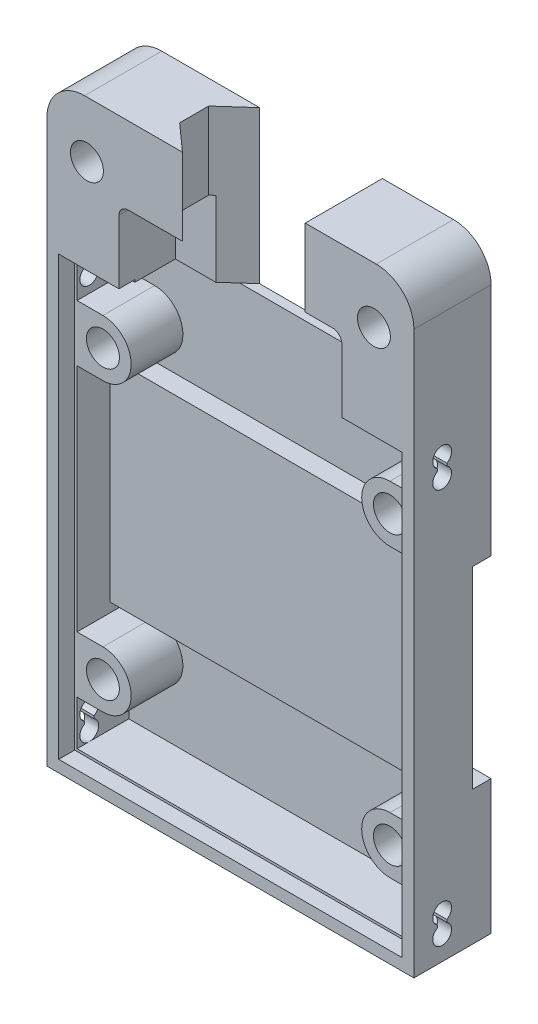
SolidWorks part; units mm, degrees
ref_plane "Front Plane" through (0, 0, 0) normal (0, 0, 1) x (1, 0, 0)
ref_plane "Top Plane" through (0, 0, 0) normal (0, 1, 0) x (1, 0, 0)
ref_plane "Right Plane" through (0, 0, 0) normal (1, 0, 0) x (0, 0, -1)
sketch "Sketch1" plane through (0, 0, 0) normal (0, 0, 1) x (1, 0, 0)
  line L0 (15.25, -20.35) -> (18, -20.35)
  line L1 (-19.5, -32.6) -> (19.5, -32.6)
  line L2 (-19.5, -32.6) -> (-19.5, 31.1)
  line L3 (-19.5, 31.1) -> (19.5, 31.1)
  line L4 (19.5, -32.6) -> (19.5, 31.1)
  line L5 (-15.25, -20.35) -> (-18, -20.35)
  line L6 (15.25, -26.35) -> (18, -26.35)
  line L7 (15.5, 31.1) -> (-15.5, 31.1) construction
  line L8 (-18, -31.1) -> (-18, 29.6)
  line L9 (-18, 29.6) -> (18, 29.6)
  line L10 (18, -31.1) -> (18, 29.6)
  line L11 (-18, -31.1) -> (18, -31.1)
  line L12 (-18, 14.9) -> (18, 14.9)
  line L13 (7.85, 14.9) -> (-4.95, 14.9) construction
  line L14 (-15.25, 4.15) -> (-18, 4.15)
  line L15 (-15.25, 10.15) -> (-18, 10.15)
  line L16 (15.25, 10.15) -> (18, 10.15)
  line L17 (15.25, 4.15) -> (18, 4.15)
  line L18 (-15.25, -26.35) -> (-18, -26.35)
  arc A0 (19.5, 27.1) -> (15.5, 31.1) centre (15.5, 27.1) ccw construction
  arc A1 (-15.5, 31.1) -> (-19.5, 27.1) centre (-15.5, 27.1) ccw construction
  arc A2 (19.5, 27.1) -> (15.5, 31.1) centre (15.5, 27.1) ccw
  arc A3 (-15.5, 31.1) -> (-19.5, 27.1) centre (-15.5, 27.1) ccw
  arc A4 (-15.5, 29.6) -> (-18, 27.1) centre (-15.5, 27.1) ccw
  arc A5 (18, 27.1) -> (15.5, 29.6) centre (15.5, 27.1) ccw
  circle A6 centre (-15.25, -23.35) radius 1.75
  circle A7 centre (15.25, -23.35) radius 1.75
  circle A8 centre (-15.25, 7.15) radius 1.75
  circle A9 centre (15.25, 7.15) radius 1.75
  circle A10 centre (15.25, 25.15) radius 1.75
  circle A11 centre (-15.25, 25.15) radius 1.75
  circle A12 centre (-15.25, -23.35) radius 3
  circle A13 centre (15.25, -23.35) radius 3
  circle A14 centre (15.25, 7.15) radius 3
  circle A15 centre (-15.25, 7.15) radius 3
  dimension "D2" = 1.5
  dimension "D4" = 6
  dimension "D3" = 3.5
  dimension "D1" = 1.5
extrude "Base shape" add sketch "Sketch1" along normal up to surface (8.2 mm away) contours L10 A5 L9 A4 L8 L12 A11 A10 | L3 A3 L2 L1 L4 A2 A15 L8 L9 L10 A14 A13 L11 A12 | A4 L9 L8 | A5 L10 L9 | A15 L15 L8 | A15 L8 A8 | A15 L8 L14 | L8 A15 | A14 L17 L10 | L10 A14 A9 | L10 A14 | A14 L10 L16 | A13 L6 L10 | L10 A13 A7 | L10 A13 | A13 L10 L0 | A12 L8 L18 | A12 L8 A6 | L8 A12 | A12 L5 L8 region at (16.8481, -20.9099, 0) region at (17.3601, -20.8437, 0) region at (17.3601, -25.8563, 0) region at (18.1004, -23.35, 0) region at (17.3601, 4.6437, 0) region at (16.8481, 4.7099, 0) region at (18.1004, 7.15, 0) region at (17.3601, 9.6563, 0) region at (-17.3601, -25.8563, 0) region at (0, 22.1041, 0) region at (-18.1004, -23.35, 0) region at (-17.9169, -23.35, 0) region at (17.4416, 29.0416, 0) region at (-17.3601, -20.8437, 0) region at (-17.3601, 9.6563, 0) region at (-17.4416, 29.0416, 0) region at (-16.8481, 9.5901, 0) region at (-18.1004, 7.15, 0) region at (-17.3601, 4.6437, 0) region at (-18.7531, -2.75, 0)
sketch "Sketch3" plane through (19.5, 0, 0) normal (1, 0, 0) x (0, 0, -1)
  line L1 (0, -18.35) -> (-2, -18.35)
  line L2 (0, -18.35) -> (0, 2.15)
  line L3 (0, 2.15) -> (-2, 2.15)
  line L4 (-2, -18.35) -> (-2, 2.15)
  line L5 (0, -18.35) -> (2, -18.35) construction
  line L6 (0, 2.15) -> (2, 2.15) construction
  line L7 (0, -32.6) -> (0, 27.1) construction
  dimension "D1" = 2
extrude "Strap cut" cut sketch "Sketch3" against normal through all
sketch "Sketch4" plane through (0, 31.1, 0) normal (0, 1, 0) x (1, 0, 0)
  line L2 (7.95, 0) -> (-5.0998, 0)
  line L4 (-15.5, 0) -> (15.5, 0) construction
  line L5 (-15.5, -8.2) -> (15.5, -8.2) construction
  line L6 (7.95, -8.2) -> (-5.0998, -8.2)
  line L12 (7.95, -8.3) -> (7.95, 0.1)
  line L13 (7.95, 0.1) -> (-4.9883, 0.1)
  line L14 (-4.9883, 0.1) -> (-7.95, -2.5553)
  line L15 (-7.95, -2.5553) -> (-7.95, -5.6447)
  line L16 (-7.95, -5.6447) -> (-4.9883, -8.3)
  line L17 (-4.9883, -8.3) -> (7.95, -8.3)
  line L18 (7.95, -8.3) -> (7.95, 0.1)
  line L19 (7.95, 0.1) -> (-4.9883, 0.1)
  line L20 (-4.9883, 0.1) -> (-7.95, -2.5553)
  line L21 (-7.95, -2.5553) -> (-7.95, -5.6447)
  line L22 (-7.95, -5.6447) -> (-4.9883, -8.3)
  line L23 (-4.9883, -8.3) -> (7.95, -8.3)
  dimension "D1" = 0.1
extrude "XT60 cut" cut sketch "Sketch4" against normal up to next contours L21 L22 L18 L20 region at (0.4142, 31.1, 4.1)
sketch "Sketch5" plane through (19.5, 0, 0) normal (1, 0, 0) x (0, 0, -1)
  line L1 (-8.2, -32.6) -> (-8.2, 27.1) construction
  line L2 (-6.2, -31.1) -> (-4.2, -31.1)
  line L3 (-6.2, -31.1) -> (-6.2, -27.1)
  line L4 (-6.2, -27.1) -> (-4.2, -27.1)
  line L5 (-4.2, -31.1) -> (-4.2, -27.1)
  line L6 (-8.2, -31.1) -> (0, -31.1) construction
  line L7 (-8.2, 14.9) -> (0, 14.9) construction
  line L8 (-6.2, 14.9) -> (-4.2, 14.9)
  line L9 (-6.2, 14.9) -> (-6.2, 10.9)
  line L10 (-6.2, 10.9) -> (-4.2, 10.9)
  line L11 (-4.2, 14.9) -> (-4.2, 10.9)
  line L14 (-5.2, -27.1) -> (-5.2, -31.1) construction
  line L15 (-5.2, 14.9) -> (-5.2, 10.9) construction
  line L16 (-5.7, -31.1) -> (-4.7, -31.1)
  line L17 (-5.7, -31.1) -> (-5.7, -27.1)
  line L18 (-5.7, -27.1) -> (-4.7, -27.1)
  line L19 (-4.7, -31.1) -> (-4.7, -27.1)
  line L20 (-5.7, -31.1) -> (-4.7, -27.1) construction
  line L21 (-5.7, -27.1) -> (-4.7, -31.1) construction
  line L23 (-5.7, 10.9) -> (-4.7, 10.9)
  line L24 (-5.7, 10.9) -> (-5.7, 14.9)
  line L25 (-5.7, 14.9) -> (-4.7, 14.9)
  line L26 (-4.7, 10.9) -> (-4.7, 14.9)
  line L27 (-5.7, 10.9) -> (-4.7, 14.9) construction
  line L28 (-5.7, 14.9) -> (-4.7, 10.9) construction
  circle A0 centre (-5.2, -28.1) radius 1
  circle A1 centre (-5.2, -30.1) radius 1
  circle A2 centre (-5.2, 13.9) radius 1
  circle A3 centre (-5.2, 11.9) radius 1
  point P20 (-5.2, -29.1)
  point P31 (-5.2, 12.9)
  dimension "D3" = 4
  dimension "D1" = 2
  dimension "D2" = 2
  dimension "D4" = 1
extrude "Power wires cut" cut sketch "Sketch5" against normal through all contours A2 L26 | L26 A2 L24 | L24 A2 | A3 A2 L24 | A3 L26 A2 | L26 A3 L24 | L24 A3 | A3 L26 | A0 L19 | L19 A0 L17 | L17 A0 | L19 A1 L17 | L17 A1 | A1 L19 | A1 L19 A0 | A1 A0 L17 region at (19.5, -30.1, 5.905) region at (19.5, -30.1, 5.2) region at (19.5, -28.1, 5.905) region at (19.5, -29.1, 5.5767) region at (19.5, -30.1, 4.495) region at (19.5, -28.1, 5.2) region at (19.5, -29.1, 4.8233) region at (19.5, -28.1, 4.495) region at (19.5, 13.9, 5.905) region at (19.5, 13.9, 5.2) region at (19.5, 11.9, 5.905) region at (19.5, 12.9, 5.5767) region at (19.5, 13.9, 4.495) region at (19.5, 11.9, 5.2) region at (19.5, 12.9, 4.8233) region at (19.5, 11.9, 4.495)
sketch "Sketch6" plane through (0, 0, 8.2) normal (0, 0, 1) x (1, 0, 0)
  line L0 (-7.85, 15.9) -> (-7.85, 21.9) construction
  line L1 (-8.85, 22.9) -> (-10.85, 22.9) construction
  line L2 (-11.85, 15.9) -> (-11.85, 21.9) construction
  line L3 (-8.85, 14.9) -> (-10.85, 14.9) construction
  line L4 (-7.85, 15.9) -> (-7.85, 21.9)
  line L5 (-8.85, 22.9) -> (-10.85, 22.9)
  line L6 (-11.85, 15.9) -> (-11.85, 21.9)
  line L7 (-8.85, 14.9) -> (-10.85, 14.9)
  line L8 (7.85, 15.9) -> (7.85, 21.9) construction
  line L9 (8.85, 22.9) -> (10.85, 22.9) construction
  line L10 (11.85, 15.9) -> (11.85, 21.9) construction
  line L11 (8.85, 14.9) -> (10.85, 14.9) construction
  line L12 (7.85, 15.9) -> (7.85, 21.9)
  line L13 (8.85, 22.9) -> (10.85, 22.9)
  line L14 (11.85, 15.9) -> (11.85, 21.9)
  line L15 (8.85, 14.9) -> (10.85, 14.9)
  line L17 (-11.85, 15.9) -> (-7.85, 15.9)
  line L18 (-11.85, 15.9) -> (-11.85, 14.9)
  line L19 (-11.85, 14.9) -> (-7.85, 14.9)
  line L20 (-7.85, 15.9) -> (-7.85, 14.9)
  line L22 (11.85, 15.9) -> (7.85, 15.9)
  line L23 (11.85, 15.9) -> (11.85, 14.9)
  line L24 (11.85, 14.9) -> (7.85, 14.9)
  line L25 (7.85, 15.9) -> (7.85, 14.9)
  line L26 (-18, 14.9) -> (-5.0998, 14.9) construction
  line L27 (11.85, 21.9) -> (7.85, 21.9)
  line L28 (11.85, 21.9) -> (11.85, 22.9)
  line L29 (11.85, 22.9) -> (7.85, 22.9)
  line L30 (7.85, 21.9) -> (7.85, 22.9)
  line L31 (-8.85, 22.9) -> (7.95, 22.9)
  line L32 (-8.85, 22.9) -> (-8.85, 14.9)
  line L33 (-8.85, 14.9) -> (7.95, 14.9)
  line L34 (7.95, 22.9) -> (7.95, 14.9)
  line L35 (7.95, 14.9) -> (18, 14.9) construction
  line L36 (7.95, 14.9) -> (7.95, 31.1) construction
  arc A0 (-8.85, 14.9) -> (-7.85, 15.9) centre (-8.85, 15.9) ccw construction
  arc A1 (-7.85, 21.9) -> (-8.85, 22.9) centre (-8.85, 21.9) ccw construction
  arc A2 (-10.85, 22.9) -> (-11.85, 21.9) centre (-10.85, 21.9) ccw construction
  arc A3 (-11.85, 15.9) -> (-10.85, 14.9) centre (-10.85, 15.9) ccw construction
  arc A4 (-8.85, 14.9) -> (-7.85, 15.9) centre (-8.85, 15.9) ccw
  arc A5 (-7.85, 21.9) -> (-8.85, 22.9) centre (-8.85, 21.9) ccw
  arc A6 (-10.85, 22.9) -> (-11.85, 21.9) centre (-10.85, 21.9) ccw
  arc A7 (-11.85, 15.9) -> (-10.85, 14.9) centre (-10.85, 15.9) ccw
  arc A8 (8.85, 22.9) -> (7.85, 21.9) centre (8.85, 21.9) ccw construction
  arc A9 (11.85, 21.9) -> (10.85, 22.9) centre (10.85, 21.9) ccw construction
  arc A10 (10.85, 14.9) -> (11.85, 15.9) centre (10.85, 15.9) ccw construction
  arc A11 (7.85, 15.9) -> (8.85, 14.9) centre (8.85, 15.9) ccw construction
  arc A12 (8.85, 22.9) -> (7.85, 21.9) centre (8.85, 21.9) ccw
  arc A13 (11.85, 21.9) -> (10.85, 22.9) centre (10.85, 21.9) ccw
  arc A14 (10.85, 14.9) -> (11.85, 15.9) centre (10.85, 15.9) ccw
  arc A15 (7.85, 15.9) -> (8.85, 14.9) centre (8.85, 15.9) ccw
  line M1 (7.95, 31.1) -> (7.95, 14.9)
  line M15 (-5.0998, 14.9) -> (-5.0998, 31.1)
extrude "IO wires cut" cut sketch "Sketch6" against normal blind 6 contours L33 L25 L12 L30 L31 M15 | A5 L4 L20 L31 M15 | L4 A5 L32 L17 | L5 A6 L6 L17 L32 | A7 L18 | L17 A7 L32 | L32 A4 L17 | A4 L20 | A12 L29 L30 M1 | L27 L12 L22 M1 | L22 A15 M1 | A15 L25 L24 L34 | A15 L34 | A15 A14 L22 M1 | A14 L23 | L14 L27 L22 M1 | L27 A13 L13 A12 L34 | A12 L29 M1 region at (-8.3587, 19.2964, 8.2) region at (-8.4256, 15.4756, 8.2) region at (-6.4903, 18.9365, 8.2) region at (-8.0734, 15.1234, 8.2) region at (-10.2516, 15.4213, 8.2) region at (-10.3368, 19.3662, 8.2) region at (-11.6266, 15.1234, 8.2) region at (1.3751, 18.9, 8.2) region at (7.8959, 15.2606, 8.2) region at (7.8959, 22.5394, 8.2) region at (8.1604, 15.056, 8.2) region at (7.9, 18.9, 8.2) region at (7.9098, 15.7354, 8.2) region at (8.1604, 22.744, 8.2) region at (9.8661, 15.4307, 8.2) region at (9.9, 18.9, 8.2) region at (9.8661, 22.3693, 8.2) region at (11.6266, 15.1234, 8.2)
sketch "Sketch7" plane through (-18, 0, 0) normal (1, 0, 0) x (0, 0, -1)
  line L6 (0, -18.35) -> (0, -20.35)
  line L7 (-2, -18.35) -> (0, -18.35)
  line L8 (-2, 2.15) -> (-2, -18.35)
  line L9 (0, 2.15) -> (-2, 2.15)
  line L12 (0, 3.15) -> (-3, 3.15)
  line L13 (-3, 3.15) -> (-3, -19.35)
  line L14 (-3, -19.35) -> (-1, -19.35)
  line L15 (-1, -19.35) -> (-1, -20.35)
  line L16 (-1, -20.35) -> (0, -20.35)
  line L17 (0, 3.15) -> (-1, 3.15)
  line L19 (0, -31.1) -> (-1, -31.1)
  line L22 (0, -31.1) -> (0, -20.35)
  line L23 (0, -20.35) -> (-1, -20.35)
  line L24 (-1, -31.1) -> (-1, -20.35)
  line L25 (0, 3.15) -> (0, 14.9)
  line L26 (0, 14.9) -> (-1, 14.9)
  line L27 (-1, 3.15) -> (-1, 14.9)
  line L28 (-5.2, 14.9) -> (0, 14.9) construction
  line L31 (0, -20.35) -> (0, -18.35) construction
  line L32 (0, 2.15) -> (-2, 2.15) construction
  line M48 (0, -20.35) -> (0, -18.35)
  line M49 (0, -18.35) -> (-2, -18.35)
  line M50 (-2, -18.35) -> (-2, 2.15)
  line M51 (-2, 2.15) -> (0, 2.15)
  line M52 (0, 2.15) -> (0, 4.15)
  line M53 (0, 4.15) -> (-8.2, 4.15)
  line M55 (-8.2, -20.35) -> (0, -20.35)
  dimension "D1" = 1
extrude "Bottom" add sketch "Sketch7" along normal up to surface (36 mm away) contours L27 L25 L26 M53 | L27 L12 M52 M53 | L14 L15 L12 L13 M55 M48 M49 M50 M51 M52 | L24 L19 L22 M55 region at (-18, -8.5273, 2.2091) region at (-18, -25.725, 0.5) region at (-18, 3.65, 0.5) region at (-18, 9.525, 0.5) up to face at (18, -8.1, 2.55)
sketch "Sketch9" plane through (0, 0, 0) normal (0, 0, -1) x (-1, 0, 0)
  circle A0 centre (-15.25, -23.35) radius 1.75 construction
  circle A1 centre (-15.25, 7.15) radius 1.75 construction
  circle A2 centre (15.25, 7.15) radius 1.75 construction
  circle A3 centre (15.25, -23.35) radius 1.75 construction
  circle A4 centre (-15.25, -23.35) radius 1.75
  circle A5 centre (-15.25, 7.15) radius 1.75
  circle A6 centre (15.25, 7.15) radius 1.75
  circle A7 centre (15.25, -23.35) radius 1.75
extrude "Bottom holes" cut sketch "Sketch9" against normal up to next
sketch "Sketch8" plane through (0, 0, 8.2) normal (0, 0, 1) x (1, 0, 0)
  line L0 (-6.2152, 14.9) -> (-18, 14.9) construction
  line L1 (-18.25, 15.15) -> (18.25, 15.15)
  line L2 (-18.25, 15.15) -> (-18.25, -31.35)
  line L3 (-18.25, -31.35) -> (18.25, -31.35)
  line L4 (18.25, 15.15) -> (18.25, -31.35)
  line L5 (-18, 14.9) -> (-18.25, 14.9) construction
  line L6 (-18, 14.9) -> (-18, 15.15) construction
  line L7 (18, 14.9) -> (18.25, 14.9) construction
  line L8 (-18, -31.1) -> (-18, -31.35) construction
  dimension "D1" = 0.25
extrude "PCB cut" cut sketch "Sketch8" against normal blind 1.7
sketch "Sketch10" [suppressed] plane through (0, 0, 2) normal (0, 0, -1) x (-1, 0, 0)
  line L0 (0, 2.15) -> (0, -18.35) construction
  line L1 (19.5, 2.15) -> (-19.5, 2.15) construction
  line L2 (19.5, -18.35) -> (-19.5, -18.35) construction
  line L3 (19.5, 2.15) -> (19.5, -18.35) construction
  line L4 (-19.5, 1.15) -> (19.5, 1.15)
  line L5 (-19.5, 1.15) -> (-19.5, 0.65)
  line L6 (-19.5, 0.65) -> (19.5, 0.65)
  line L7 (19.5, 1.15) -> (19.5, 0.65)
  line L8 (-19.5, 1.15) -> (19.5, 0.65) construction
  line L9 (-19.5, 0.65) -> (19.5, 1.15) construction
  line L10 (-19.5, 2.15) -> (19.5, 2.15) construction
  line L11 (-19.5, -1.35) -> (19.5, -1.35)
  line L12 (19.5, -0.85) -> (19.5, -1.35)
  line L13 (-19.5, -0.85) -> (19.5, -0.85)
  line L14 (-19.5, -0.85) -> (-19.5, -1.35)
  line L15 (-19.5, -3.35) -> (19.5, -3.35)
  line L16 (19.5, -2.85) -> (19.5, -3.35)
  line L17 (-19.5, -2.85) -> (19.5, -2.85)
  line L18 (-19.5, -2.85) -> (-19.5, -3.35)
  line L19 (-19.5, -5.35) -> (19.5, -5.35)
  line L20 (19.5, -4.85) -> (19.5, -5.35)
  line L21 (-19.5, -4.85) -> (19.5, -4.85)
  line L22 (-19.5, -4.85) -> (-19.5, -5.35)
  line L23 (-19.5, -7.35) -> (19.5, -7.35)
  line L24 (19.5, -6.85) -> (19.5, -7.35)
  line L25 (-19.5, -6.85) -> (19.5, -6.85)
  line L26 (-19.5, -6.85) -> (-19.5, -7.35)
  line L27 (-19.5, -9.35) -> (19.5, -9.35)
  line L28 (19.5, -8.85) -> (19.5, -9.35)
  line L29 (-19.5, -8.85) -> (19.5, -8.85)
  line L30 (-19.5, -8.85) -> (-19.5, -9.35)
  line L31 (-19.5, -11.35) -> (19.5, -11.35)
  line L32 (19.5, -10.85) -> (19.5, -11.35)
  line L33 (-19.5, -10.85) -> (19.5, -10.85)
  line L34 (-19.5, -10.85) -> (-19.5, -11.35)
  line L35 (-19.5, -13.35) -> (19.5, -13.35)
  line L36 (19.5, -12.85) -> (19.5, -13.35)
  line L37 (-19.5, -12.85) -> (19.5, -12.85)
  line L38 (-19.5, -12.85) -> (-19.5, -13.35)
  line L39 (-19.5, -15.35) -> (19.5, -15.35)
  line L40 (19.5, -14.85) -> (19.5, -15.35)
  line L41 (-19.5, -14.85) -> (19.5, -14.85)
  line L42 (-19.5, -14.85) -> (-19.5, -15.35)
  line L43 (-19.5, -17.35) -> (19.5, -17.35)
  line L44 (19.5, -16.85) -> (19.5, -17.35)
  line L45 (-19.5, -16.85) -> (19.5, -16.85)
  line L46 (-19.5, -16.85) -> (-19.5, -17.35)
  point P6 (0, 0.9)
  dimension "D1" = 1
  dimension "D2" = 0.5
  dimension "D4" = 2
  dimension "D3" = 10
extrude "Boss-Extrude1" [suppressed] add sketch "Sketch10" along normal up to surface (2 mm away) up to face at (13.5, 7.15, 0)
